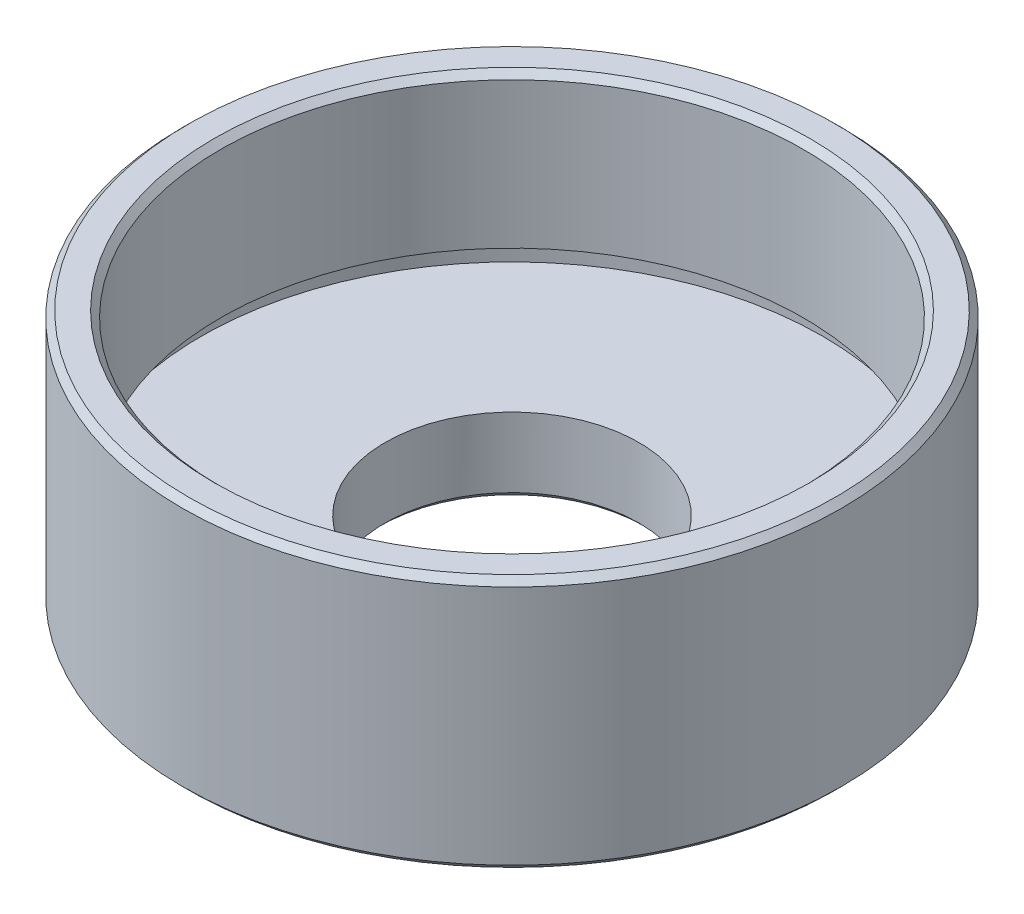
SolidWorks part; units mm, degrees
material "AISI 304"
ref_plane "Спереди" through (0, 0, 0) normal (0, 0, 1) x (1, 0, 0)
ref_plane "Сверху" through (0, 0, 0) normal (0, 1, 0) x (1, 0, 0)
ref_plane "Справа" through (0, 0, 0) normal (1, 0, 0) x (0, 0, -1)
ref_axis "ОсьX" through (-88.99, 0, 0) along (1, 0, 0)
ref_axis "ОсьZ" through (0, 55, 0) along (0, -1, 0)
ref_axis "ОсьY" through (0, 0, -88.99) along (0, 0, 1)
sketch "Эскиз1" plane through (0, 0, 0) normal (0, 0, 1) x (1, 0, 0)
  line L0 (-26, 20) -> (-26, 0)
  line L1 (0, 26.169) -> (0, -22.1581) construction
  line L2 (-26, 0) -> (-10, 0)
  line L3 (-10, 0) -> (-10, 6)
  line L4 (-10, 6) -> (-24.5, 6)
  line L6 (-24.5, 8) -> (-23, 8)
  line L7 (-23, 8) -> (-23, 20)
  line L8 (-23, 20) -> (-26, 20)
  line L11 (-24.5, 8) -> (-24.5, 6)
  dimension "D1" = 52
  dimension "D2" = 20
  dimension "D3" = 46
  dimension "D4" = 20
  dimension "D5" = 6
  dimension "D6" = 1.5
  dimension "D9" = 12
revolve "Повернуть1" add sketch "Эскиз1" angle 360 mid plane about L1
cosmetic thread "Условное изображение резьбы1" parameters "D2"=48
chamfer "Фаска1" distance 0.5 angle 45 4 edges at (0, 0, 10) (0, 0, 26) (0, 20, 26) (0, 20, 23)
